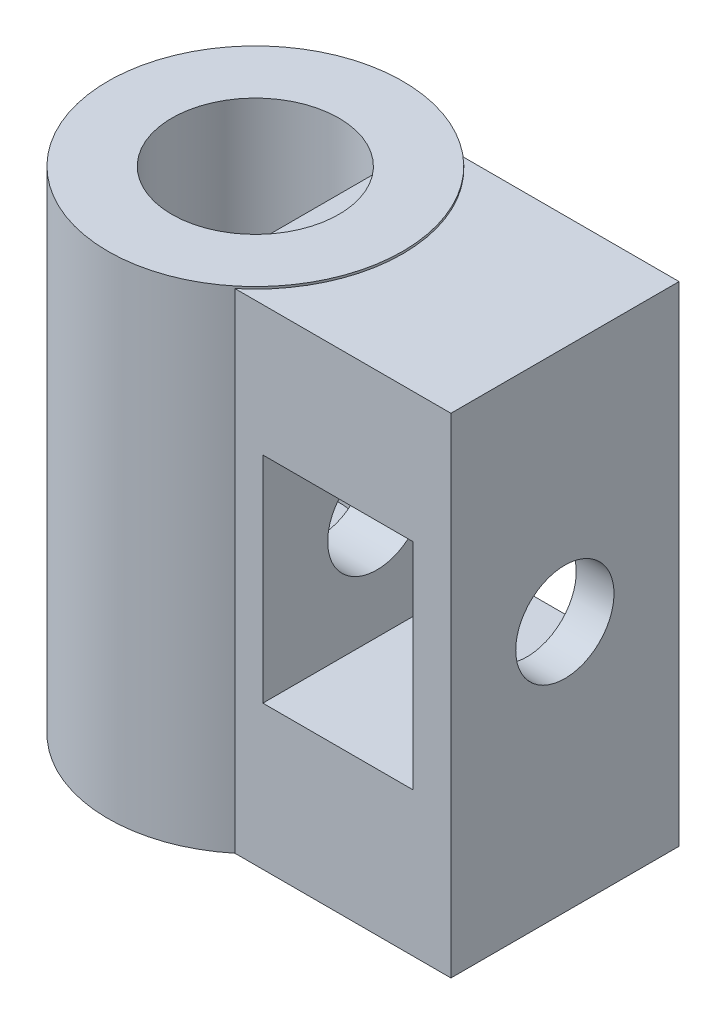
SolidWorks part; units mm, degrees
ref_plane "Front Plane" through (0, 0, 0) normal (0, 0, 1) x (1, 0, 0)
ref_plane "Top Plane" through (0, 0, 0) normal (0, 1, 0) x (1, 0, 0)
ref_plane "Right Plane" through (0, 0, 0) normal (1, 0, 0) x (0, 0, -1)
sketch "Sketch1" plane through (0, 0, 0) normal (0, 1, 0) x (1, 0, 0)
  circle A0 centre (0, 0) radius 6
extrude "Boss-Extrude1" add sketch "Sketch1" along normal blind 20
sketch "Sketch2" plane through (0, 20, 0) normal (0, 1, 0) x (1, 0, 0)
  circle A0 centre (0, 0) radius 3.4
extrude "Cut-Extrude1" cut sketch "Sketch2" against normal blind 13.55 contours A0
ref_plane "Plane1" through (0, 18.26, 0) normal (0, 1, 0) x (1, 0, 0)
ref_axis "Axis1" through (0, 6.45, 0) along (0, 1, 0)
ref_point "Point2"
sketch "Sketch5" plane through (0, 18.26, 0) normal (0, 1, 0) x (1, 0, 0)
  line L0 (0, 0) -> (2.6, 0) construction
  line L2 (2.6, -3.5716) -> (4.1507, -3.5716)
  line L3 (2.6, -3.5716) -> (2.6, 3.6126)
  line L4 (2.6, 3.6126) -> (4.1507, 3.6126)
  line L5 (4.1507, -3.5716) -> (4.1507, 3.6126)
extrude "Boss-Extrude2" add sketch "Sketch5" against normal blind 13.55
sketch "Sketch7" plane through (2.6, 0, 0) normal (-1, 0, 0) x (0, 0, 1)
  line L1 (-4.6485, 19.91) -> (4.638, 19.91)
  line L2 (-4.6485, 19.91) -> (-4.6485, 0)
  line L3 (-4.6485, 0) -> (4.638, 0)
  line L4 (4.638, 19.91) -> (4.638, 0)
extrude "Boss-Extrude3" add sketch "Sketch7" against normal blind 10
sketch "Sketch6" plane through (2.6, 0, 0) normal (-1, 0, 0) x (0, 0, 1)
  line L1 (-2.1909, 6.45) -> (-2.1909, 19.91) construction
  line L2 (2.1909, 19.91) -> (2.1909, 6.45) construction
  line L3 (-2.1909, 15.4522) -> (2.1909, 15.4522) construction
  circle A0 centre (0, 10.2369) radius 2
  point P0 (0, 10.2369)
  point P12 (0, 0)
extrude "Cut-Extrude2" cut sketch "Sketch6" against normal blind 13.55 and the other way blind 1
ref_axis "Axis2" through (-1.8994, 10.2369, 0) along (-1, 0, 0)
ref_axis "Axis4" through (12.6, 10.2369, 0) along (-1, 0, 0)
ref_plane "Plane3" through (0, 0, 0) normal (0, 0, 1) x (1, 0, 0)
sketch "Sketch9" plane through (0, 0, 0) normal (0, 0, 1) x (1, 0, 0)
  line L0 (11.0634, 10.2369) -> (11.0634, 5.8619)
  line L1 (4.9434, 5.8619) -> (11.0634, 5.8619)
  line L2 (4.9434, 5.8619) -> (4.9434, 10.2369)
  line L3 (4.9434, 10.2369) -> (4.9434, 14.6119)
  line L4 (4.9434, 14.6119) -> (11.0634, 14.6119)
  line L5 (11.0634, 14.6119) -> (11.0634, 10.2369)
  line L6 (12.6, 10.2369) -> (2.6, 10.2369) construction
  point P5 (10.3875, 10.2369)
  point P9 (4.9434, 10.2369)
extrude "Cut-Extrude3" cut sketch "Sketch9" against normal blind 10 and the other way blind 10
